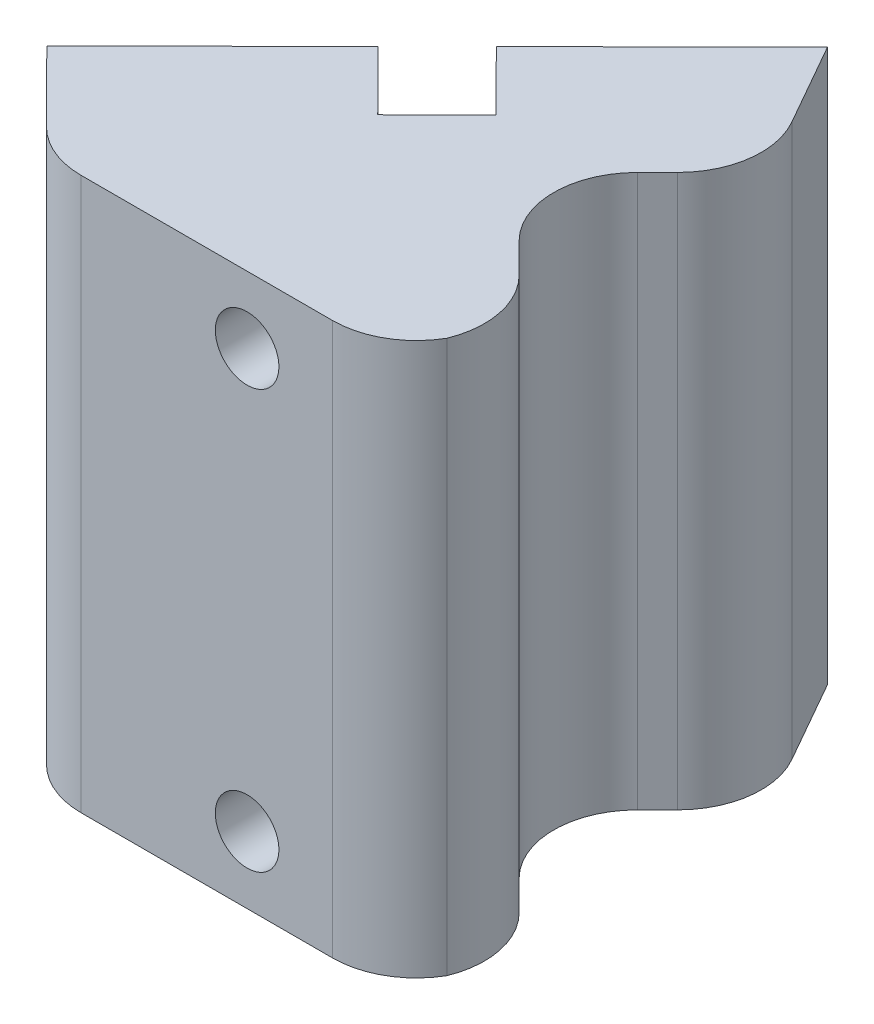
SolidWorks part; units mm, degrees
ref_plane "Front Plane" through (0, 0, 0) normal (0, 0, 1) x (1, 0, 0)
ref_plane "Top Plane" through (0, 0, 0) normal (0, 1, 0) x (1, 0, 0)
ref_plane "Right Plane" through (0, 0, 0) normal (1, 0, 0) x (0, 0, -1)
sketch "Sketch1" plane through (0, 0, 0) normal (0, 1, 0) x (1, 0, 0)
  line L0 (0, 0) -> (20, 0)
  line L1 (20, 0) -> (30.9278, 18.9274)
  line L2 (30.9278, 18.9274) -> (0, 0) construction
  line L3 (0, 0) -> (23.389, 23.2799)
  line L4 (30.9278, 18.9274) -> (23.389, 23.2799)
  dimension "D1" = 120
  dimension "D2" = 20
  dimension "D3" = 33
  dimension "D4" = 13.4
  dimension "D5" = 90
extrude "Boss-Extrude1" add sketch "Sketch1" along normal blind 33
sketch "Sketch2" plane through (0, 0, 0) normal (0.7055, 0, 0.7088) x (0.7088, 0, -0.7055)
  line L1 (0, 0) -> (33, 0)
  line L2 (0, 0) -> (0, 33)
  line L3 (0, 33) -> (33, 33)
  line L4 (33, 0) -> (33, 33)
extrude "Boss-Extrude2" add sketch "Sketch2" against normal blind 3
sketch "Sketch3" plane through (30, 0, 0) normal (0, 0, -1) x (-1, 0, 0)
  line L0 (18, -986.4883) -> (18, 49013.5117) construction
  line L1 (-972.5, 16.5) -> (49027.5, 16.5) construction
  line L3 (30, 33) -> (30, 0) construction
  line L4 (30, 33) -> (10, 33) construction
  circle A0 centre (18, 29) radius 1.9
  circle A1 centre (18, 4) radius 1.9
  dimension "D2" = 3.8
  dimension "D3" = 3.8
  dimension "D1" = 12
  dimension "D4" = 12.5
  dimension "D5" = 12.5
  dimension "D6" = 16.5
extrude "Cut-Extrude1" cut sketch "Sketch3" along normal blind 7
fillet "Fillet1" radius 5 1 edges at (20, 16.5, 0)
sketch "Sketch5" plane through (-2.1164, 0, -2.1263) normal (-0.7055, 0, -0.7088) x (-0.7088, 0, 0.7055)
  line L0 (-33, 16.5) -> (0, 16.5) construction
  line L3 (-16.5, 33) -> (-16.5, 0) construction
  line L8 (0, 33) -> (0, 0) construction
  line L9 (-33, 33) -> (0, 33) construction
  line L10 (0, 0) -> (-33, 0) construction
  line L11 (-33, 33) -> (-33, 0) construction
  circle A0 centre (-29.3, 28.4) radius 2
  circle A1 centre (-3.7, 28.4) radius 2
  circle A2 centre (-29.3, 4.6) radius 2
  circle A3 centre (-3.7, 4.6) radius 2
  dimension "D6" = 4
  dimension "D7" = 4
  dimension "D8" = 4
  dimension "D9" = 4
  dimension "D1" = 12.8
  dimension "D2" = 12.8
  dimension "D3" = 12.8
  dimension "D4" = 12.8
  dimension "D5" = 11.9
  dimension "D10" = 11.9
  dimension "D11" = 11.9
  dimension "D12" = 11.9
extrude "Boss-Extrude3" add sketch "Sketch5" along normal blind 5
sketch "Sketch6" plane through (-2.1164, 0, -2.1263) normal (-0.7055, 0, -0.7088) x (-0.7088, 0, 0.7055)
  line L0 (-31, 31) -> (-31, 2)
  line L1 (-33, 33) -> (0, 33)
  line L2 (-33, 33) -> (-33, 0)
  line L3 (-33, 0) -> (0, 0)
  line L4 (0, 33) -> (0, 0)
  line L5 (-31, 2) -> (-2, 2)
  line L6 (-2, 31) -> (-2, 2)
  line L7 (-31, 31) -> (-2, 31)
  dimension "D1" = 2
extrude "Boss-Extrude4" add sketch "Sketch6" along normal blind 5
sketch "Sketch9" plane through (-2.1164, 0, -2.1263) normal (-0.7055, 0, -0.7088) x (-0.7088, 0, 0.7055)
  line L0 (-27.3, 28.4) -> (-27.3, 31)
  line L1 (-2, 31) -> (-31, 31) construction
  line L3 (-27.3, 31) -> (-31, 31)
  line L5 (-31, 31) -> (-31, 26.6111)
  line L6 (-31, 31) -> (-31, 29.4536) construction
  line L7 (-31, 26.6111) -> (-28.4056, 26.6111)
  line L8 (-28.4056, 26.6111) -> (-27.3, 28.4)
  line L9 (-5.7, 28.4) -> (-5.7, 31)
  line L10 (-5.7, 31) -> (-2, 31)
  line L11 (-2, 31) -> (-2, 26.6111)
  line L12 (-2, 2) -> (-2, 3.5464) construction
  line L13 (-2, 26.6111) -> (-4.5944, 26.6111)
  line L14 (-4.5944, 26.6111) -> (-5.7, 28.4)
  line L15 (-4.5944, 6.3889) -> (-2, 6.3889)
  line L16 (-2, 2) -> (-2, 3.5464) construction
  line L17 (-2, 6.3889) -> (-2, 2)
  line L18 (-2, 2) -> (-4.9, 2)
  line L19 (-31, 2) -> (-2, 2) construction
  line L20 (-4.9, 2) -> (-4.9, 6.2)
  line L21 (-4.9, 6.2) -> (-4.5944, 6.3889)
  line L22 (-27.3, 4.6) -> (-27.3, 2)
  line L23 (-31, 2) -> (-2, 2) construction
  line L24 (-27.3, 2) -> (-31, 2)
  line L25 (-31, 2) -> (-31, 6.3889)
  line L26 (-31, 31) -> (-31, 29.4536) construction
  line L27 (-31, 6.3889) -> (-28.4056, 6.3889)
  line L28 (-28.4056, 6.3889) -> (-27.3, 4.6)
  circle A0 centre (-29.3, 28.4) radius 2 construction
  circle A1 centre (-29.3, 28.4) radius 2 construction
  circle A2 centre (-3.7, 28.4) radius 2 construction
  circle A3 centre (-3.7, 28.4) radius 2 construction
  circle A4 centre (-3.7, 4.6) radius 2 construction
  circle A5 centre (-3.7, 4.6) radius 2 construction
  circle A6 centre (-29.3, 4.6) radius 2 construction
  circle A7 centre (-29.3, 4.6) radius 2 construction
extrude "Boss-Extrude5" add sketch "Sketch9" along normal blind 5
sketch "Sketch7" plane through (-5.6436, 0, -5.6701) normal (-0.7055, 0, -0.7088) x (-0.7088, 0, 0.7055)
  line L1 (-5.7, 31) -> (-27.3, 31) construction
  line L2 (-19, 73.6996) -> (-14, 73.6996)
  line L3 (-19, 73.6996) -> (-19, -11.6996)
  line L4 (-19, -11.6996) -> (-14, -11.6996)
  line L5 (-14, 73.6996) -> (-14, -11.6996)
  line L6 (-19, 73.6996) -> (-14, -11.6996) construction
  line L8 (-19, -11.6996) -> (-14, 73.6996) construction
  circle A0 centre (-29.3, 28.4) radius 0.75
  circle A1 centre (-3.7, 28.4) radius 0.75
  circle A2 centre (-3.7, 4.6) radius 0.75
  circle A3 centre (-29.3, 4.6) radius 0.75
  point P0 (-16.5, 31)
  dimension "D3" = 1.5
  dimension "D4" = 1.5
  dimension "D5" = 1.5
  dimension "D6" = 1.5
  dimension "D1" = 5
extrude "Cut-Extrude3" cut sketch "Sketch7" against normal blind 5
sketch "Sketch8" plane through (0, 33, 0) normal (0, 1, 0) x (1, 0, 0)
  line L0 (17.7453, 28.95) -> (16.8781, 39.6256)
  line L1 (16.8781, 39.6256) -> (45.2125, 18.1015)
  line L2 (45.2125, 18.1015) -> (33.0366, 2.0731)
  line L3 (17.7453, 28.95) -> (33.0366, 2.0731)
extrude "Cut-Extrude4" cut sketch "Sketch8" against normal through all
sketch "Sketch10" plane through (0, 33, 0) normal (0, 1, 0) x (1, 0, 0)
  line L0 (22.4528, 20.6759) -> (15.018, 13.2412)
  line L1 (17.7453, 28.95) -> (27.1602, 12.4018) construction
  line L2 (15.018, 13.2412) -> (23.0231, 5.2361)
  line L3 (21.4434, 2.5) -> (27.1602, 12.4018) construction
  line L4 (23.0231, 5.2361) -> (31.8398, 14.0529)
  line L5 (31.8398, 14.0529) -> (22.4528, 20.6759)
extrude "Cut-Extrude5" cut sketch "Sketch10" against normal through all
fillet "Fillet4" radius 5 4 edges at (23.0231, 16.5, -5.2361) (15.018, 16.5, -13.2412) (22.4528, 16.5, -20.6759) (0, 16.5, 0)
equation "\"D2@Sketch5\"=\"D1@Sketch5\""
equation "\"D3@Sketch5\"=\"D1@Sketch5\""
equation "\"D4@Sketch5\"=\"D1@Sketch5\""
equation "\"D7@Sketch5\"=\"D6@Sketch5\""
equation "\"D9@Sketch5\"=\"D6@Sketch5\""
equation "\"D8@Sketch5\"=\"D6@Sketch5\""
equation "\"D10@Sketch5\"=\"D5@Sketch5\""
equation "\"D11@Sketch5\"=\"D5@Sketch5\""
equation "\"D12@Sketch5\"=\"D5@Sketch5\""
